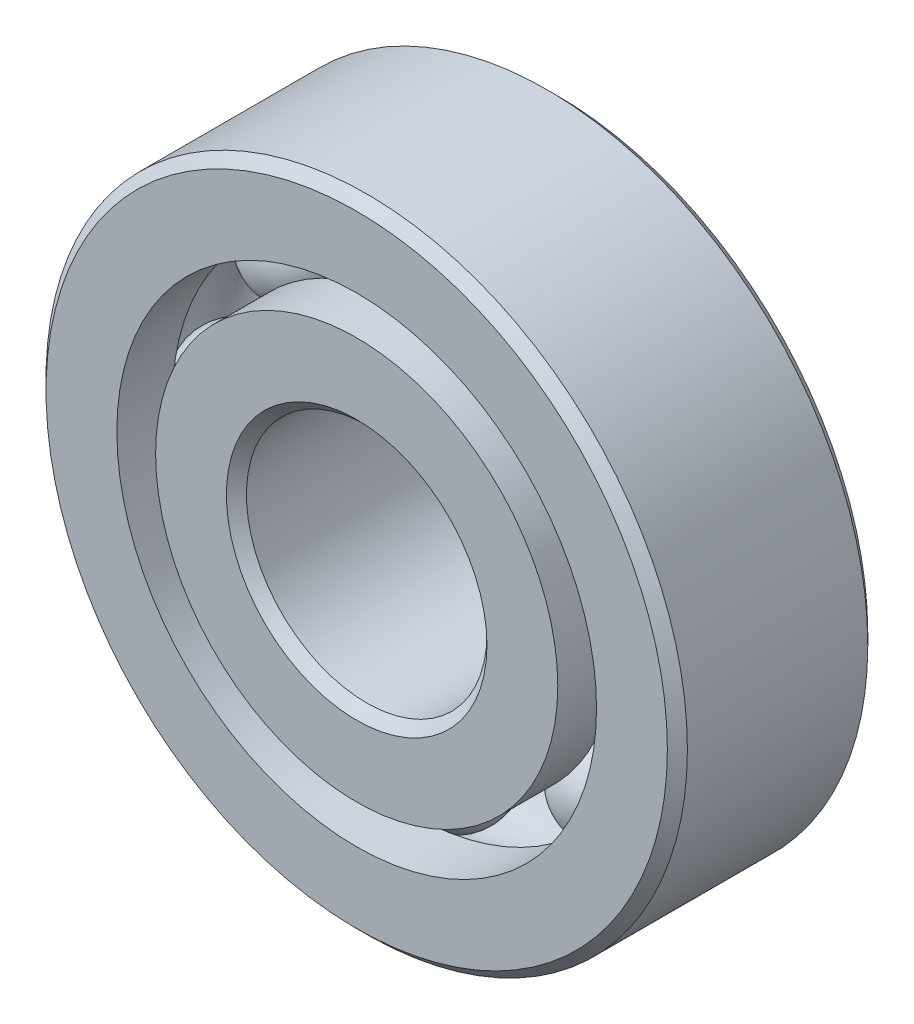
SolidWorks part; units mm, degrees
ref_plane "Front Plane" through (0, 0, 0) normal (0, 0, 1) x (1, 0, 0)
ref_plane "Top Plane" through (0, 0, 0) normal (0, 1, 0) x (1, 0, 0)
ref_plane "Right Plane" through (0, 0, 0) normal (1, 0, 0) x (0, 0, -1)
sketch "Sketch1" plane through (0, 0, 0) normal (1, 0, 0) x (0, 0, -1)
  line L0 (-1.9844, 0) -> (1.9844, 0) construction
  line L1 (0, 6.35) -> (0, -6.35) construction
  line L2 (1.7859, 6.35) -> (-1.7859, 6.35)
  line L3 (-1.7859, 6.35) -> (-1.9844, 6.1516)
  line L4 (-1.9844, 6.1516) -> (-1.9844, 4.7494)
  line L5 (-1.9844, 4.7494) -> (-0.8819, 4.7494)
  line L6 (1.9844, 4.7494) -> (0.8819, 4.7494)
  line L7 (1.9844, 6.1516) -> (1.9844, 4.7494)
  line L8 (1.7859, 6.35) -> (1.9844, 6.1516)
  line L9 (0, 6.35) -> (0, 4.3656) construction
  line L10 (0, 4.3656) -> (0, 2.3812) construction
  arc A0 (-0.8819, 4.7494) -> (0.8819, 4.7494) centre (0, 4.3656) cw
  point P14 (0, 2.3812)
  dimension "D3" = 1.7639
  dimension "D1" = 45
  dimension "Width" = 3.9688
  dimension "OD" = 12.7
  dimension "D2" = 0.1984
  dimension "Shaft Dia" = 4.7625
  dimension "D4" = 0.3838
revolve "Revolve1" add sketch "Sketch1" angle 360 about L0
sketch "Sketch3" plane through (0, 0, 0) normal (1, 0, 0) x (0, 0, -1)
  line L0 (-1.9844, 3.9818) -> (-0.8819, 3.9818)
  line L1 (0, 6.35) -> (0, -6.35) construction
  line L2 (-1.9844, 6.1516) -> (-1.9844, 4.7494) construction
  line L3 (-1.9844, 3.9818) -> (-1.9844, 2.5797)
  line L4 (-1.7859, 6.35) -> (-1.9844, 6.1516) construction
  line L5 (-1.9844, 2.5797) -> (-1.7859, 2.3812)
  line L6 (-1.7859, 2.3812) -> (1.7859, 2.3812)
  line L7 (1.7859, 6.35) -> (1.7859, -6.35) construction
  line L8 (1.7859, 2.3812) -> (1.9844, 2.5797)
  line L9 (1.9844, -6.1516) -> (1.9844, 6.1516) construction
  line L10 (1.9844, 2.5797) -> (1.9844, 3.9818)
  line L11 (1.9844, 3.9818) -> (0.8819, 3.9818)
  line L13 (1.7859, 6.35) -> (1.9844, 6.1516) construction
  arc A0 (0.8819, 4.7494) -> (-0.8819, 4.7494) centre (0, 4.3656) ccw construction
  arc A1 (0.8819, 3.9818) -> (-0.8819, 3.9818) centre (0, 4.3656) cw
revolve "Revolve3" add sketch "Sketch3" angle 360 about L0
sketch "Sketch4" plane through (0, 0, 0) normal (1, 0, 0) x (0, 0, -1)
  line L0 (-0.9618, 4.3656) -> (0.9618, 4.3656)
  arc A2 (-0.9618, 4.3656) -> (0.9618, 4.3656) centre (0, 4.3656) cw
  arc A3 (0.8819, 4.7494) -> (-0.8819, 4.7494) centre (0, 4.3656) ccw construction
revolve "Revolve4" add sketch "Sketch4" angle 360 about L0
ref_axis "Axis1" through (0, 0, -1.9844) along (0, 0, 1)
pattern_circular "CirPattern1" count 8 every 45 about axis through (0, 0, -1.9844) along (0, 0, 1) of bodies 104
sketch "Sketch5" plane through (0, 0, 0) normal (1, 0, 0) x (0, 0, -1)
  line L0 (-1.9844, 4.7494) -> (-0.8819, 4.7494) construction
  line L1 (-1.8852, 4.7494) -> (-0.9618, 4.7494)
  line L2 (-1.8852, 4.7494) -> (-1.8852, 3.9818)
  line L3 (-1.8852, 3.9818) -> (-0.9618, 3.9818)
  line L4 (-0.9618, 4.7494) -> (-0.9618, 3.9818)
  line L5 (-1.9844, 3.9818) -> (-0.8819, 3.9818) construction
  line L6 (1.9844, 4.7494) -> (0.8819, 4.7494) construction
  line L7 (1.8852, 4.7494) -> (0.9618, 4.7494)
  line L8 (1.8852, 4.7494) -> (1.8852, 3.9818)
  line L9 (1.8852, 3.9818) -> (0.9618, 3.9818)
  line L10 (0.9618, 4.7494) -> (0.9618, 3.9818)
  line L11 (1.9844, 3.9818) -> (0.8819, 3.9818) construction
  line L12 (-1.7859, 6.35) -> (-1.9844, 6.1516) construction
  point P18 (-1.8852, 6.2508)
revolve "Revolve5" [suppressed] add sketch "Sketch5" angle 360 about L0
equation "\"D2@Sketch1\" = \"Width@Sketch1\"*.05"
equation "\"D3@Sketch1\" = \"Width@Sketch1\"/2.25"
equation "\"D4@Sketch1\" = (((\"OD@Sketch1\"-\"Width@Sketch1\")/2)/3.25)/3.5"
equation "\"D2@CirPattern1\" = 360/\"Balls@CirPattern1\""
